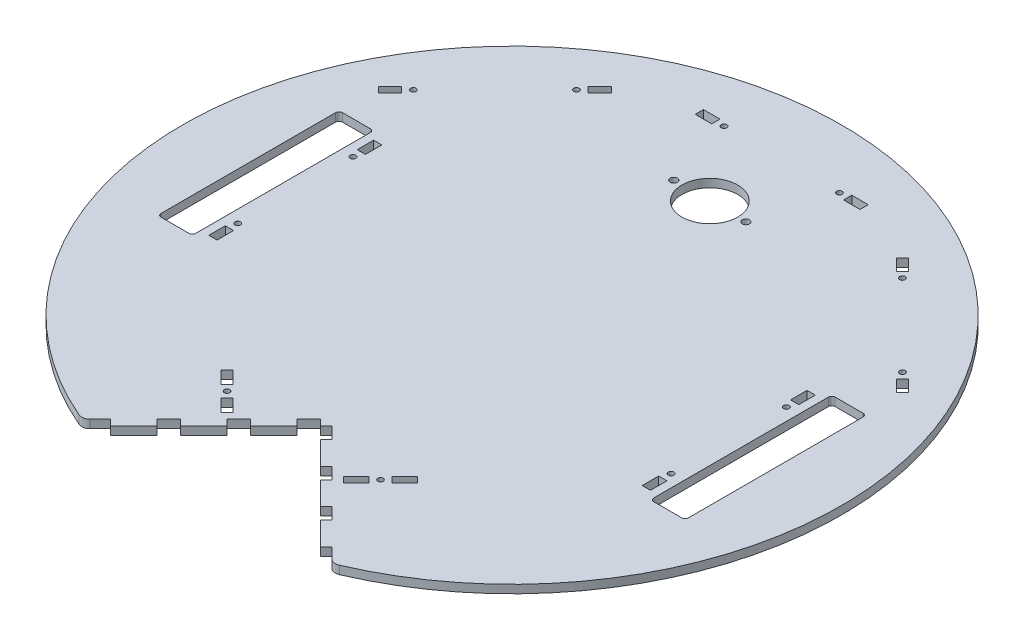
SolidWorks part; units mm, degrees
ref_plane "Front Plane" through (0, 0, 0) normal (0, 0, 1) x (1, 0, 0)
ref_plane "Top Plane" through (0, 0, 0) normal (0, 1, 0) x (1, 0, 0)
ref_plane "Right Plane" through (0, 0, 0) normal (1, 0, 0) x (0, 0, -1)
sketch "Sketch1" plane through (0, 0, 0) normal (0, 1, 0) x (1, 0, 0)
  circle A0 centre (0, 0) radius 254
  dimension "D1" = 508
extrude "Boss-Extrude1" add sketch "Sketch1" along normal blind 6.35
sketch "Sketch2" plane through (0, 6.35, 0) normal (0, 1, 0) x (1, 0, 0)
  line L0 (0, -147.7927) -> (-89.8026, -237.5952)
  line L1 (0, -36.2008) -> (0, -54.9716) construction
  line L2 (0, -147.7927) -> (89.8026, -237.5952)
  circle A0 centre (0, 0) radius 254 construction
  arc A1 (-89.8026, -237.5952) -> (89.8026, -237.5952) centre (0, 0) ccw
  dimension "D1" = 127
  dimension "D2" = 45
extrude "Cut-Extrude2" cut sketch "Sketch2" against normal through all
sketch "Sketch3" plane through (0, 6.35, 0) normal (0, 1, 0) x (1, 0, 0)
  line L0 (-31.4309, -170.2433) -> (-26.9408, -165.7532)
  line L1 (-31.4309, -170.2433) -> (-40.4112, -161.2631)
  line L2 (-26.9408, -165.7532) -> (-35.921, -156.7729)
  line L3 (-40.4112, -161.2631) -> (-35.921, -156.7729)
  line L4 (0, -147.7927) -> (-89.8026, -237.5952) construction
  line L5 (89.8026, -237.5952) -> (0, -147.7927) construction
  line L6 (-38.1661, -159.018) -> (-41.2194, -155.9647) construction
  circle A0 centre (-41.2194, -155.9647) radius 2.159
  dimension "D5" = 4.318
  dimension "D1" = 6.35
  dimension "D2" = 12.7
  dimension "D3" = 31.75
  dimension "D4" = 6.35
  dimension "D6" = 4.318
extrude "Cut-Extrude3" [suppressed] cut sketch "Sketch3" against normal through all
mirror "Mirror1" [suppressed] about plane through (0, 0, 0) normal (1, 0, 0)
sketch "Sketch4" plane through (0, 6.35, 0) normal (0, 1, 0) x (1, 0, 0)
  line L0 (0, 54.2551) -> (0, 121.7464) construction
  line L1 (-200.66, 69.85) -> (-179.07, 69.85)
  line L2 (-203.2, 67.31) -> (-203.2, -67.31)
  line L3 (-200.66, -69.85) -> (-179.07, -69.85)
  line L4 (-176.53, 67.31) -> (-176.53, -67.31)
  line L5 (-17.8666, 0) -> (24.1783, 0) construction
  line L6 (-254, -69.5481) -> (-254, -224.3367) construction
  arc A0 (-200.66, -69.85) -> (-203.2, -67.31) centre (-200.66, -67.31) cw
  arc A1 (-179.07, -69.85) -> (-176.53, -67.31) centre (-179.07, -67.31) ccw
  arc A2 (-176.53, 67.31) -> (-179.07, 69.85) centre (-179.07, 67.31) ccw
  arc A3 (-200.66, 69.85) -> (-203.2, 67.31) centre (-200.66, 67.31) ccw
  arc A4 (89.8026, -237.5952) -> (-89.8026, -237.5952) centre (0, 0) ccw construction
  dimension "D5" = 2.54
  dimension "D4" = 2.54
  dimension "D1" = 26.67
  dimension "D2" = 50.8
  dimension "D3" = 139.7
extrude "Cut-Extrude4" cut sketch "Sketch4" against normal through all
mirror "Mirror2" about plane through (0, 0, 0) normal (1, 0, 0) of "Cut-Extrude4"
sketch "Sketch6" plane through (0, 6.35, 0) normal (0, 1, 0) x (1, 0, 0)
  line L0 (-35.921, -183.7137) -> (-94.7317, -124.903) construction
  line L1 (0, -147.7927) -> (-89.8026, -237.5952) construction
  line L2 (89.8026, -237.5952) -> (0, -147.7927) construction
  line B0 (-61.3685, -153.7761) -> (-71.1005, -144.0441)
  line B1 (-61.3685, -153.7761) -> (-65.8586, -158.2663)
  line B2 (-71.1005, -144.0441) -> (-75.5906, -148.5343)
  line B3 (-65.8586, -158.2663) -> (-75.5906, -148.5343)
  line B4 (-52.3882, -162.7564) -> (-42.6562, -172.4884)
  line B5 (-56.8783, -167.2465) -> (-47.1463, -176.9785)
  line B6 (-42.6562, -172.4884) -> (-47.1463, -176.9785)
  line B7 (-52.3882, -162.7564) -> (-56.8783, -167.2465)
  circle B8 centre (-59.1234, -160.5113) radius 2.0955
  dimension "D1" = 50.8
  dimension "D2" = 12.7
sketch_block_instance "BoltTab-1"
sketch_block "BoltTab" parameters "D1"=4.191, "D2"=6.35, "D3"=6.35
extrude "Cut-Extrude6" cut sketch "Sketch6" against normal through all
mirror "Mirror5" about plane through (0, 0, 0) normal (1, 0, 0) of "Cut-Extrude6"
sketch "Sketch8" plane through (0, 0, 0) normal (0, -1, 0) x (1, 0, 0)
  line L0 (-170.18, -63.5) -> (-170.18, -50.8) construction
  line L1 (-170.18, -63.5) -> (-163.83, -63.5) construction
  line L2 (-163.83, -63.5) -> (-163.83, -50.8) construction
  line L3 (-170.18, -50.8) -> (-163.83, -50.8) construction
  line L4 (-170.18, -63.5) -> (-170.18, -50.8)
  line L5 (-170.18, -63.5) -> (-163.83, -63.5)
  line L6 (-163.83, -63.5) -> (-163.83, -50.8)
  line L7 (-170.18, -50.8) -> (-163.83, -50.8)
  line L8 (-170.18, 50.8) -> (-163.83, 50.8) construction
  line L9 (-170.18, 63.5) -> (-170.18, 50.8) construction
  line L10 (-163.83, 63.5) -> (-163.83, 50.8) construction
  line L11 (-170.18, 63.5) -> (-163.83, 63.5) construction
  line L12 (-170.18, 50.8) -> (-163.83, 50.8)
  line L13 (-170.18, 63.5) -> (-170.18, 50.8)
  line L14 (-163.83, 63.5) -> (-163.83, 50.8)
  line L15 (-170.18, 63.5) -> (-163.83, 63.5)
  line L16 (-170.18, -46.5836) -> (-163.83, -46.5836) construction
  line L17 (-170.18, -42.3164) -> (-163.83, -42.3164) construction
  line L18 (-170.18, -46.5836) -> (-163.83, -46.5836) construction
  line L19 (-170.18, -42.3164) -> (-163.83, -42.3164) construction
  line L20 (-167.005, -42.3164) -> (-167.005, -46.5836) construction
  line L21 (-170.18, 42.3164) -> (-163.83, 42.3164) construction
  line L22 (-170.18, 46.5836) -> (-163.83, 46.5836) construction
  line L23 (-170.18, 42.3164) -> (-163.83, 42.3164) construction
  line L24 (-170.18, 46.5836) -> (-163.83, 46.5836) construction
  line L25 (-167.005, 42.3164) -> (-167.005, 46.5836) construction
  circle A0 centre (-167.005, -44.45) radius 2.1336
  circle A1 centre (-167.005, 44.45) radius 2.1336
extrude "Cut-Extrude7" cut sketch "Sketch8" against normal through all
mirror "Mirror6" about plane through (0, 0, 0) normal (1, 0, 0) of "Cut-Extrude7"
sketch "Sketch9" plane through (0, 0, 0) normal (0, -1, 0) x (1, 0, 0)
  line L0 (-63.5, -204.6423) -> (-63.5, -210.9923) construction
  line L1 (-63.5, -204.6423) -> (-50.8, -204.6423) construction
  line L2 (-50.8, -204.6423) -> (-50.8, -210.9923) construction
  line L3 (-63.5, -210.9923) -> (-50.8, -210.9923) construction
  line L4 (-63.5, -204.6423) -> (-63.5, -210.9923)
  line L5 (-63.5, -204.6423) -> (-50.8, -204.6423)
  line L6 (-50.8, -204.6423) -> (-50.8, -210.9923)
  line L7 (-63.5, -210.9923) -> (-50.8, -210.9923)
  line L8 (-46.5836, -204.6423) -> (-46.5836, -210.9923) construction
  line L9 (-42.3164, -204.6423) -> (-42.3164, -210.9923) construction
  line L10 (-46.5836, -204.6423) -> (-46.5836, -210.9923) construction
  line L11 (-42.3164, -204.6423) -> (-42.3164, -210.9923) construction
  line L12 (-46.5836, -207.8173) -> (-42.3164, -207.8173) construction
  line L13 (42.3164, -204.6423) -> (42.3164, -210.9923) construction
  line L14 (46.5836, -204.6423) -> (46.5836, -210.9923) construction
  line L15 (42.3164, -204.6423) -> (42.3164, -210.9923) construction
  line L16 (46.5836, -204.6423) -> (46.5836, -210.9923) construction
  line L17 (50.8, -210.9923) -> (63.5, -210.9923)
  line L18 (63.5, -210.9923) -> (63.5, -204.6423)
  line L19 (63.5, -204.6423) -> (50.8, -204.6423)
  line L20 (50.8, -204.6423) -> (50.8, -210.9923)
  line L21 (50.8, -210.9923) -> (63.5, -210.9923)
  line L22 (63.5, -210.9923) -> (63.5, -204.6423)
  line L23 (63.5, -204.6423) -> (50.8, -204.6423)
  line L24 (50.8, -204.6423) -> (50.8, -210.9923)
  line L25 (42.3164, -207.8173) -> (46.5836, -207.8173) construction
  circle A0 centre (-44.45, -207.8173) radius 2.1336
  circle A1 centre (44.45, -207.8173) radius 2.1336
  dimension "D1" = 0
extrude "Cut-Extrude8" cut sketch "Sketch9" against normal through all
sketch "Sketch10" plane through (0, 0, 0) normal (0, -1, 0) x (1, 0, 0)
  line L0 (-204.1857, -101.143) -> (-195.2055, -110.1232) construction
  line L1 (-195.2055, -110.1232) -> (-190.7153, -105.6331) construction
  line L2 (-190.7153, -105.6331) -> (-199.6956, -96.6529) construction
  line L3 (-199.6956, -96.6529) -> (-204.1857, -101.143) construction
  line L4 (-123.3634, -181.9653) -> (-114.3832, -190.9455) construction
  line L5 (-114.3832, -190.9455) -> (-109.893, -186.4554) construction
  line L6 (-109.893, -186.4554) -> (-118.8733, -177.4752) construction
  line L7 (-118.8733, -177.4752) -> (-123.3634, -181.9653) construction
  line L8 (-204.1857, -101.143) -> (-195.2055, -110.1232)
  line L9 (-195.2055, -110.1232) -> (-190.7153, -105.6331)
  line L10 (-190.7153, -105.6331) -> (-199.6956, -96.6529)
  line L11 (-199.6956, -96.6529) -> (-204.1857, -101.143)
  line L12 (-123.3634, -181.9653) -> (-114.3832, -190.9455)
  line L13 (-114.3832, -190.9455) -> (-109.893, -186.4554)
  line L14 (-109.893, -186.4554) -> (-118.8733, -177.4752)
  line L15 (-118.8733, -177.4752) -> (-123.3634, -181.9653)
  line L16 (-187.7339, -108.6146) -> (-192.224, -113.1047) construction
  line L17 (-184.7165, -111.6319) -> (-189.2067, -116.122) construction
  line L18 (-124.8721, -171.4763) -> (-129.3622, -175.9665) construction
  line L19 (-121.8547, -174.4937) -> (-126.3449, -178.9838) construction
  line L20 (-187.7339, -108.6146) -> (-192.224, -113.1047) construction
  line L21 (-184.7165, -111.6319) -> (-189.2067, -116.122) construction
  line L22 (-124.8721, -171.4763) -> (-129.3622, -175.9665) construction
  line L23 (-121.8547, -174.4937) -> (-126.3449, -178.9838) construction
  line L25 (-186.9616, -113.877) -> (-189.979, -110.8596) construction
  line L26 (-127.1172, -173.7214) -> (-124.0998, -176.7388) construction
  circle A0 centre (-188.4703, -112.3683) radius 2.1336
  circle A1 centre (-125.6085, -175.2301) radius 2.1336
extrude "Cut-Extrude9" cut sketch "Sketch10" against normal through all
mirror "Mirror7" about plane through (0, 0, 0) normal (1, 0, 0) of "Cut-Extrude9"
sketch "Sketch11" plane through (0, 6.35, 0) normal (0, 1, 0) x (1, 0, 0)
  line L0 (0, 61.4305) -> (0, 100.7164) construction
  line L1 (-82.8279, 254) -> (68.7629, 254) construction
  circle A0 centre (0, 152.4) radius 21.463
  arc A1 (89.8026, -237.5952) -> (-89.8026, -237.5952) centre (0, 0) ccw construction
  circle A2 centre (27.7813, 152.4) radius 2.7781 construction
  circle A3 centre (-27.7813, 152.4) radius 2.7781 construction
  circle A4 centre (27.7813, 152.4) radius 2.7781
  circle A5 centre (-27.7813, 152.4) radius 2.7781
  dimension "D1" = 42.926
  dimension "D2" = 101.6
extrude "Cut-Extrude10" cut sketch "Sketch11" against normal through all
sketch "Sketch12" plane through (73.8963, 0, 73.8963) normal (0.7071, 0, 0.7071) x (0.7071, 0, -0.7071)
  line L0 (-218.8052, 6.35) -> (-218.8052, 0) construction
  line L1 (-244.2052, 6.35) -> (-218.8052, 6.35)
  line L2 (-244.2052, 6.35) -> (-244.2052, 0)
  line L3 (-244.2052, 0) -> (-218.8052, 0)
  line L4 (-218.8052, 6.35) -> (-218.8052, 0)
  line L5 (-104.5052, 0) -> (-231.5052, 0) construction
  line L6 (-104.5052, 6.35) -> (-231.5052, 6.35) construction
  line L7 (-193.4052, 6.35) -> (-180.7052, 6.35)
  line L8 (-193.4052, 6.35) -> (-193.4052, 0)
  line L9 (-193.4052, 0) -> (-180.7052, 0)
  line L10 (-180.7052, 6.35) -> (-180.7052, 0)
  line L11 (-193.4052, 0) -> (-193.4052, 6.35) construction
  line L12 (-180.7052, 6.35) -> (-180.7052, 0) construction
  line L13 (-155.3052, 0) -> (-155.3052, 6.35) construction
  line L14 (-155.3052, 6.35) -> (-142.6052, 6.35)
  line L15 (-155.3052, 6.35) -> (-155.3052, 0)
  line L16 (-155.3052, 0) -> (-142.6052, 0)
  line L17 (-142.6052, 6.35) -> (-142.6052, 0)
  line L18 (-142.6052, 6.35) -> (-142.6052, 0) construction
  line L19 (-117.2052, 0) -> (-117.2052, 6.35) construction
  line L20 (-117.2052, 6.35) -> (-104.5052, 6.35)
  line L21 (-117.2052, 6.35) -> (-117.2052, 0)
  line L22 (-117.2052, 0) -> (-104.5052, 0)
  line L23 (-104.5052, 6.35) -> (-104.5052, 0)
  dimension "D1" = 25.4
extrude "Cut-Extrude11" cut sketch "Sketch12" against normal blind 6.35
mirror "Mirror8" about plane through (0, 0, 0) normal (1, 0, 0) of "Cut-Extrude11"
fillet "Fillet1" radius 6.35 2 edges at (96.2464, 3.175, 235.0588) (-96.2464, 3.175, 235.0588)
